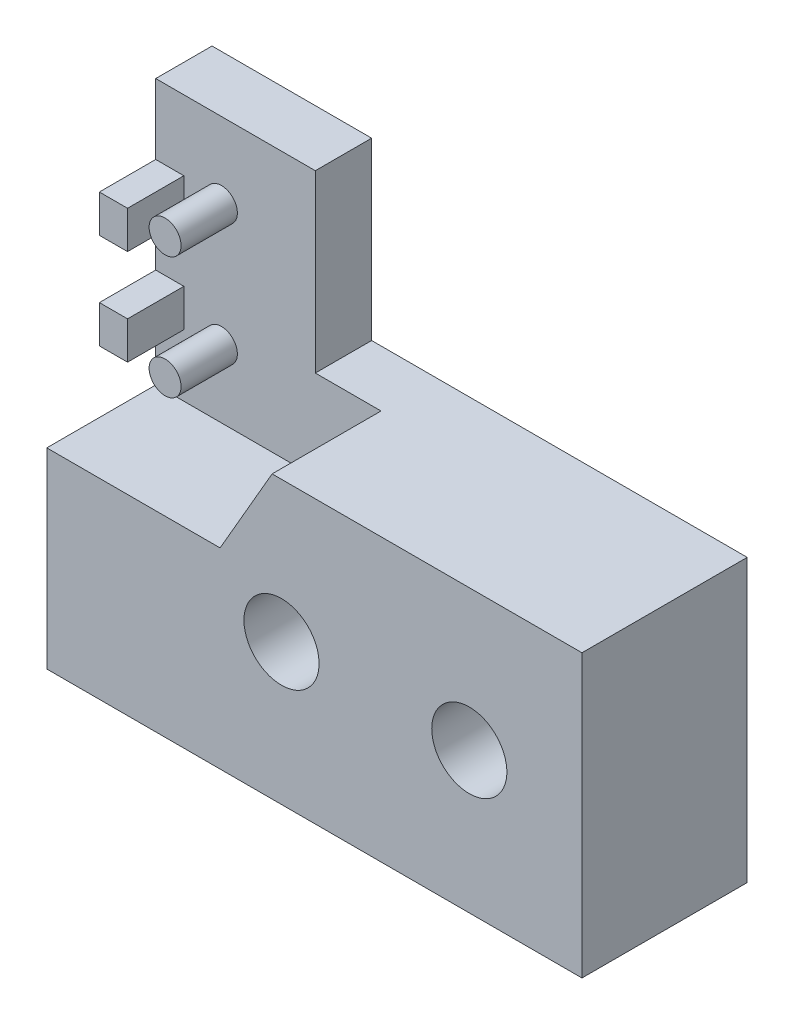
SolidWorks part; units mm, degrees
ref_plane "前视基准面" through (0, 0, 0) normal (0, 0, 1) x (1, 0, 0)
ref_plane "上视基准面" through (0, 0, 0) normal (0, 1, 0) x (1, 0, 0)
ref_plane "右视基准面" through (0, 0, 0) normal (1, 0, 0) x (0, 0, -1)
other "Configuration Table"
sketch "草图1" plane through (0, 0, 0) normal (0, 0, 1) x (1, 0, 0)
  line L0 (0, 0) -> (-28.5, 0)
  line L1 (-28.5, 0) -> (-28.5, 15)
  line L2 (-28.5, 15) -> (-8.5, 15)
  line L3 (-8.5, 15) -> (-8.5, 24.333)
  line L4 (-8.5, 24.333) -> (0, 24.333)
  line L5 (0, 24.333) -> (0, 0)
  dimension "D1" = 28.5
  dimension "D2" = 15
  dimension "D3" = 24.333
  dimension "D4" = 8.5
extrude "凸台-拉伸1" add sketch "草图1" along normal blind 3
sketch "草图2" plane through (0, 0, 3) normal (0, 0, 1) x (1, 0, 0)
  line L0 (-12, 15) -> (-9.2287, 10.2)
  line L1 (-8.5, 15) -> (-28.5, 15) construction
  line L2 (-9.2287, 10.2) -> (0, 10.2)
  line L3 (0, 0) -> (0, 24.333) construction
  line L4 (-8.5, 24.333) -> (-8.5, 15) construction
  line L5 (-12, 15) -> (-28.5, 15)
  line L6 (-28.5, 15) -> (-28.5, 0)
  line L7 (-28.5, 0) -> (0, 0)
  line L8 (0, 0) -> (0, 10.2)
  dimension "D1" = 120
  dimension "D2" = 4.8
  dimension "D3" = 3.5
extrude "凸台-拉伸2" add sketch "草图2" along normal blind 5.8
sketch "草图3" plane through (0, 0, 3) normal (0, 0, 1) x (1, 0, 0)
  line L0 (-3.5, 20.3) -> (-3.5, 13.8) construction
  line L1 (0, 10.2) -> (-9.2287, 10.2) construction
  line L2 (0, 13.5) -> (-1.5, 13.5)
  line L3 (0, 10.2) -> (0, 24.333) construction
  line L4 (-1.5, 13.5) -> (-1.5, 15.5)
  line L5 (-1.5, 15.5) -> (0, 15.5)
  line L6 (0, 10.2) -> (-9.2287, 10.2) construction
  line L7 (-3.5, 17.05) -> (0.6251, 17.05) construction
  line L8 (0, 15.6122) -> (0, 13.5)
  line L9 (0, 18.4878) -> (0, 20.6)
  line L10 (-1.5, 18.6) -> (0, 18.6)
  line L11 (-1.5, 20.6) -> (-1.5, 18.6)
  line L12 (0, 20.6) -> (-1.5, 20.6)
  circle A0 centre (-3.5, 13.8) radius 0.85
  circle A1 centre (-3.5, 20.3) radius 0.85
  line M9 (0, 10.2) -> (0, 24.333)
  dimension "D2" = 1.7
  dimension "D1" = 6.5
  dimension "D3" = 3.6
  dimension "D4" = 2
  dimension "D5" = 3.3
  dimension "D6" = 1.5
  dimension "D7" = 3.5
extrude "凸台-拉伸3" add sketch "草图3" along normal blind 3 contours L9 L12 L11 L10 | L5 L4 L2 M9 | A0 | A1 region at (-0.75, 19.6, 3) region at (-0.75, 14.5, 3) region at (-3.5, 13.8, 3) region at (-3.5, 20.3, 3)
sketch "草图5" plane through (0, 0, 8.8) normal (0, 0, 1) x (1, 0, 0)
  line L0 (-28.5, 7.5) -> (0, 7.5)
  line L1 (-28.5, 15) -> (-28.5, 0) construction
  line L2 (0, 0) -> (0, 10.2) construction
  circle A0 centre (-22.5, 7.5) radius 2
  circle A1 centre (-12.5, 7.5) radius 2
  dimension "D1" = 4
  dimension "D2" = 4
  dimension "D3" = 10
  dimension "D4" = 6
extrude "切除-拉伸1" cut sketch "草图5" against normal up to surface (8.8 mm away) contours L0 A0 | L0 A0 | L0 A1 | L0 A1 region at (-22.5, 8.3488, 8.8) region at (-12.5, 8.3488, 8.8) region at (-12.5, 6.6512, 8.8) region at (-22.5, 6.6512, 8.8) up to face at (-12.3333, 13.111, 0)
mirror "镜向2" about plane through (0, 0, 0) normal (1, 0, 0) of "凸台-拉伸1", "凸台-拉伸2", "凸台-拉伸3", "切除-拉伸1"
sketch "草图6" plane through (0, 0, 8.8) normal (0, 0, 1) x (1, 0, 0)
  line L0 (0, 0) -> (0, 29.163)
  line L1 (-28.5, 0) -> (28.5, 0) construction
  line L2 (0, 29.163) -> (-34.7523, 29.163)
  line L3 (-34.7523, 29.163) -> (-34.7523, 0)
  line L4 (-34.7523, 0) -> (0, 0)
extrude "切除-拉伸2" cut sketch "草图6" against normal blind 10
